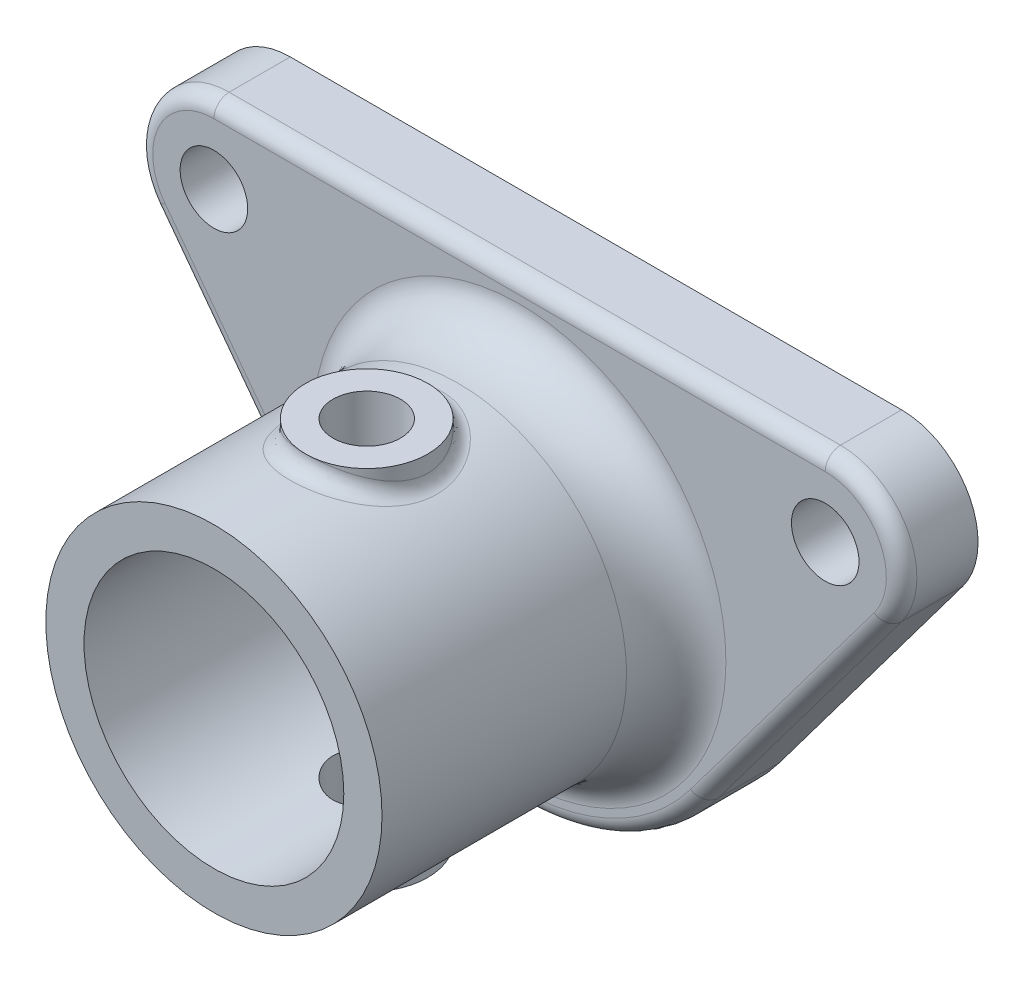
SolidWorks part; units mm, degrees
ref_plane "Front Plane" through (0, 0, 0) normal (0, 0, 1) x (1, 0, 0)
ref_plane "Top Plane" through (0, 0, 0) normal (0, 1, 0) x (1, 0, 0)
ref_plane "Right Plane" through (0, 0, 0) normal (1, 0, 0) x (0, 0, -1)
sketch "Sketch1" plane through (0, 0, 0) normal (0, 0, 1) x (1, 0, 0)
  line L0 (15.24, -11.43) -> (30.48, 8.89)
  line L1 (25.4, 19.05) -> (0, 19.05)
  line L2 (0, 45.8701) -> (0, -24.8855) construction
  line L3 (0, 19.05) -> (-25.4, 19.05)
  line L4 (-30.48, 8.89) -> (-15.24, -11.43)
  arc A0 (-15.24, -11.43) -> (15.24, -11.43) centre (0, 0) ccw
  arc A1 (30.48, 8.89) -> (25.4, 19.05) centre (25.4, 12.7) ccw
  arc A2 (-25.4, 19.05) -> (-30.48, 8.89) centre (-25.4, 12.7) ccw
  dimension "D2" = 38.1
  dimension "D3" = 19.05
  dimension "D4" = 6.35
  dimension "D1" = 25.4
extrude "Boss-Extrude1" add sketch "Sketch1" along normal blind 6.35
sketch "Sketch2" plane through (0, 0, 6.35) normal (0, 0, 1) x (1, 0, 0)
  circle A1 centre (0, 0) radius 13.97
  dimension "D2" = 27.94
extrude "Boss-Extrude2" add sketch "Sketch2" along normal blind 25.4
sketch "Sketch3" plane through (0, 0, 6.35) normal (0, 0, 1) x (1, 0, 0)
  point P0 (-25.4, 12.7)
  point P1 (25.4, 12.7)
hole_wizard "#10 Clearance Hole1" positions "Sketch4" profile "Sketch5" hole size "#10" standard "ANSI Inch" end condition through all
sketch "Sketch4" plane through (0, 0, 6.35) normal (0, 0, 1) x (1, 0, 0)
  point P0 (-25.4, 12.7)
  point P3 (25.4, 12.7)
sketch "Sketch5" plane through (-25.4, 12.7, 6.35) normal (1, 0, 0) x (0, -1, 0)
  line L0 (0, 0) -> (0, 6.35)
  line L1 (0, 6.35) -> (2.8067, 6.35)
  line L2 (2.8067, 6.35) -> (2.8067, 0)
  line L5 (2.8067, 0) -> (0, 0)
  line L11 (0, -6.35) -> (0, 107.95) construction
  dimension "Thru Hole Dia." = 5.6134
  dimension "Thru Hole Depth" = 6.35
fillet "Fillet2" radius 3.175 1 edges at (13.97, 0, 6.35) second distance 5.08 first distance on face at (-22.5933, 12.7, 6.35)
fillet "Fillet3" radius 1.27 6 edges at (22.86, -1.27, 6.35) (31.0796, 15.5398, 6.35) (0, 19.05, 6.35) (-31.0796, 15.5398, 6.35) (-22.86, -1.27, 6.35) (0, -19.05, 6.35)
sketch "Sketch7" plane through (0, 0, 0) normal (0, 1, 0) x (1, 0, 0)
  line L0 (-13.97, -31.75) -> (13.97, -31.75) construction
  circle A0 centre (0, -19.05) radius 5.08
  dimension "D2" = 10.16
  dimension "D1" = 12.7
extrude "Boss-Extrude3" add sketch "Sketch7" along normal mid plane 30.48
fillet "Fillet4" radius 1.27 2 edges at (-0.8081, -13.9466, 24.0653) (0.8081, 13.9466, 24.0653)
sketch "Sketch8" plane through (0, 0, 31.75) normal (0, 0, 1) x (1, 0, 0)
  circle A0 centre (0, 0) radius 10.795
  dimension "D1" = 21.59
extrude "Cut-Extrude1" cut sketch "Sketch8" against normal blind 25.4
hole_wizard "#10 Clearance Hole2" positions "Sketch10" profile "Sketch11" hole size "#10" standard "ANSI Inch" end condition through all
sketch "Sketch10" plane through (0, 15.24, 0) normal (0, 1, 0) x (1, 0, 0)
  point P0 (0, -19.05)
sketch "Sketch11" plane through (0, 15.24, 19.05) normal (1, 0, 0) x (0, 0, 1)
  line L0 (0, 0) -> (0, 34.29)
  line L1 (0, 34.29) -> (2.8067, 34.29)
  line L2 (2.8067, 34.29) -> (2.8067, 0)
  line L5 (2.8067, 0) -> (0, 0)
  line L11 (0, -6.35) -> (0, 107.95) construction
  dimension "Thru Hole Dia." = 5.6134
  dimension "Thru Hole Depth" = 34.29
